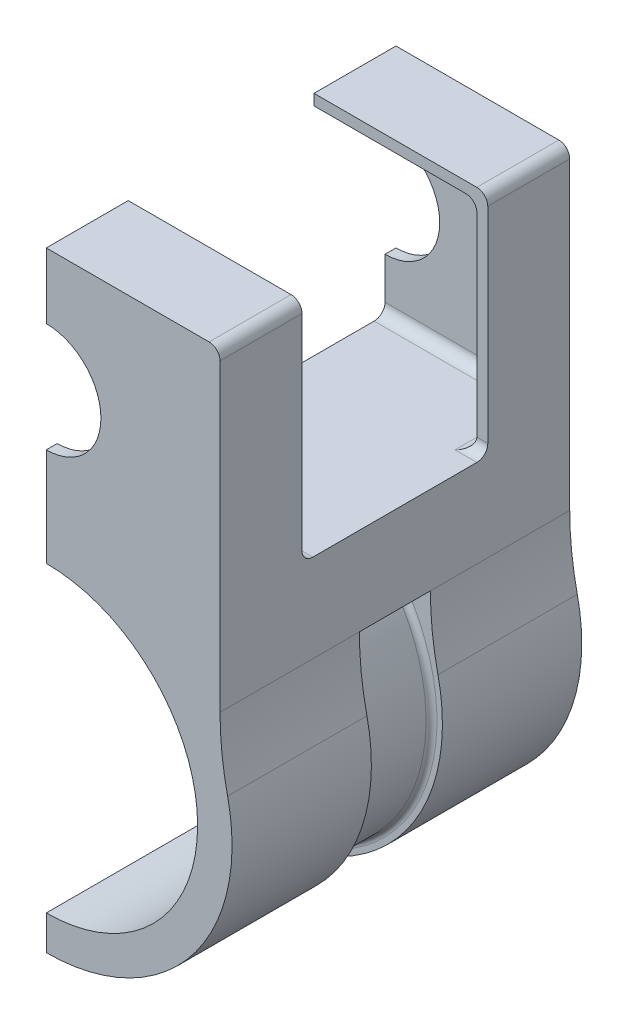
SolidWorks part; units mm, degrees
ref_plane "Front Plane" through (0, 0, 0) normal (0, 0, 1) x (1, 0, 0)
ref_plane "Top Plane" through (0, 0, 0) normal (0, 1, 0) x (1, 0, 0)
ref_plane "Right Plane" through (0, 0, 0) normal (1, 0, 0) x (0, 0, -1)
sketch "Sketch1" plane through (0, 0, 0) normal (0, 0, 1) x (1, 0, 0)
  line L0 (0, 0) -> (0, 52.959) construction
  line L1 (0, 0) -> (0, -43.18) construction
  line L2 (0, 52.959) -> (0, 58.039)
  line L3 (0, 83.439) -> (0, 98.679)
  line L4 (0, 98.679) -> (40.386, 98.679)
  line L5 (40.386, 98.679) -> (40.386, 25.3987)
  line L7 (0, 52.959) -> (0, 35.179)
  line L8 (0, -35.179) -> (0, -43.18)
  arc A0 (0, -35.179) -> (0, 35.179) centre (0, 0) ccw
  arc A1 (0, -43.18) -> (42.1474, 9.3865) centre (0, 0) ccw
  arc A2 (0, 58.039) -> (0, 83.439) centre (0, 70.739) ccw
  arc A3 (42.1474, 9.3865) -> (40.386, 25.3987) centre (114.046, 25.3987) cw
  dimension "D1" = 70.358
  dimension "D2" = 86.36
  dimension "D3" = 12.7
  dimension "D8" = 73.66
  dimension "D4" = 5.08
  dimension "D5" = 15.24
  dimension "D6" = 40.386
  dimension "D7" = 17.78
extrude "Boss-Extrude1" add sketch "Sketch1" against normal blind 81.28 contours A2 L3 L4 L5 A3 A1 L8 A0 L7 L2
sketch "Sketch3" plane through (0, 0, 0) normal (-1, 0, 0) x (0, 0, 1)
  line L0 (-78.74, 96.139) -> (-78.74, 45.847)
  line L1 (-78.74, 45.847) -> (-2.54, 45.847)
  line L2 (-2.54, 45.847) -> (-2.54, 96.139)
  line L3 (-2.54, 96.139) -> (-78.74, 96.139)
  line L4 (-81.28, 98.679) -> (0, 98.679) construction
  line L5 (-81.28, 83.439) -> (-81.28, 98.679) construction
  line L6 (0, 83.439) -> (0, 98.679) construction
  dimension "D1" = 2.54
  dimension "D2" = 2.54
  dimension "D3" = 2.54
  dimension "D4" = 50.292
extrude "Cut-Extrude1" cut sketch "Sketch3" against normal offset from surface (37.846 mm away) 2.54 up to face at (40.386, 62.0389, -40.64)
sketch "Sketch4" plane through (0, 98.679, 0) normal (0, 1, 0) x (1, 0, 0)
  line L0 (0, 62.23) -> (40.386, 62.23)
  line L2 (0, 81.28) -> (0, 0) construction
  line L3 (40.386, 81.28) -> (40.386, 0) construction
  line L4 (40.386, 62.23) -> (40.386, 19.05)
  line L5 (40.386, 81.28) -> (40.386, 0) construction
  line L6 (40.386, 19.05) -> (0, 19.05)
  line L7 (0, 19.05) -> (0, 62.23)
  line L8 (0, 81.28) -> (40.386, 81.28) construction
  line L9 (0, 0) -> (40.386, 0) construction
  dimension "D1" = 19.05
  dimension "D2" = 19.05
extrude "Cut-Extrude2" cut sketch "Sketch4" against normal up to surface (52.832 mm away) up to face at (18.923, 45.847, -40.64)
fillet "Fillet1" radius 2.54 4 edges at (18.923, 45.847, -78.74) (37.846, 45.847, -70.485) (18.923, 45.847, -2.54) (37.846, 45.847, -10.795)
fillet "Fillet2" radius 2.54 2 edges at (37.846, 96.139, -70.485) (37.846, 96.139, -10.795)
fillet "Fillet3" radius 2.54 2 edges at (37.846, 45.847, -19.05) (37.846, 45.847, -62.23)
fillet "Fillet4" radius 2.54 2 edges at (40.386, 98.679, -9.525) (40.386, 98.679, -71.755)
ref_axis "Axis1" through (0, 0, -81.28) along (0, 0, 1)
ref_plane "Plane1" through (0, -43.18, -81.28) normal (0, 0, 1) x (1, 0, 0)
sketch "Sketch7" plane through (0, 0, 0) normal (-1, 0, 0) x (0, 0, 1)
  line L0 (-81.28, -43.18) -> (0, -43.18) construction
  line L1 (-48.895, -43.18) -> (-32.385, -43.18)
  line L2 (-48.895, -43.18) -> (-48.895, -40.64)
  line L3 (-48.895, -40.64) -> (-32.385, -40.64)
  line L4 (-32.385, -43.18) -> (-32.385, -40.64)
  point P6 (-40.64, -40.64)
  point P7 (-40.64, -43.18)
  dimension "D1" = 16.51
  dimension "D2" = 2.54
revolve "Cut-Revolve2" cut sketch "Sketch7" angle 360 about axis through (0, 0, -81.28) along (0, 0, 1)
ref_plane "Plane2" through (42.1474, 9.3865, 0) normal (0.9761, 0.2174, 0) x (0, 0, -1)
sketch "Sketch8" plane through (42.1474, 9.3865, 0) normal (0.9761, 0.2174, 0) x (0, 0, -1)
  line L0 (81.28, 0) -> (0, 0) construction
  line L1 (32.385, 0) -> (48.895, 0)
  line L2 (32.385, 0) -> (32.385, 16.0122)
  line L3 (32.385, 16.0122) -> (48.895, 16.0122)
  line L4 (48.895, 0) -> (48.895, 16.0122)
  line L5 (81.28, 16.0122) -> (0, 16.0122) construction
  point P8 (40.64, 16.0122)
  point P9 (40.64, 16.0122)
  dimension "D1" = 16.51
extrude "Cut-Extrude4" cut sketch "Sketch8" against normal up to surface and the other way blind 2.54 contours L4 L3 L2 L1 up to face at (20.32, 0, -40.64)
fillet "Fillet5" radius 1.27 2 edges at (40.64, 0, -48.895) (40.64, 0, -32.385)
